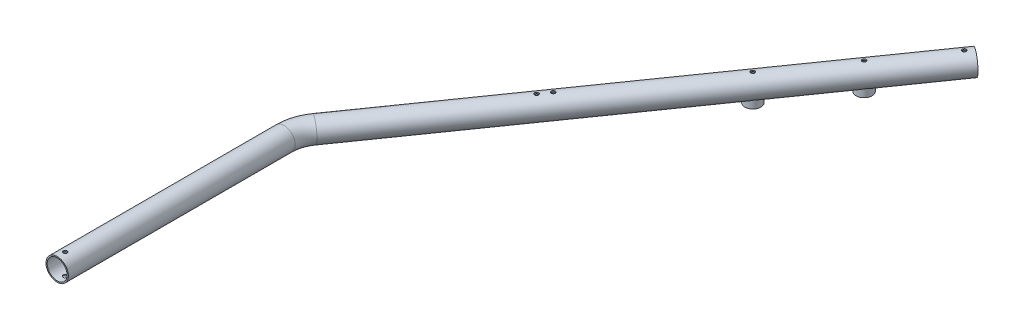
SolidWorks part; units mm, degrees
material "1060 Alloy"
ref_plane "Front Plane" through (0, 0, 0) normal (0, 0, 1) x (1, 0, 0)
ref_plane "Top Plane" through (0, 0, 0) normal (0, 1, 0) x (1, 0, 0)
ref_plane "Right Plane" through (0, 0, 0) normal (1, 0, 0) x (0, 0, -1)
sketch "Sketch2" plane through (0, 0, 0) normal (0, 1, 0) x (1, 0, 0)
  line L0 (0, 0) -> (-340.9616, -487.088)
  line L1 (-350, -515.7611) -> (-350, -800)
  arc A0 (-340.9616, -487.088) -> (-350, -515.7611) centre (-300, -515.7611) ccw
  point P6 (-350, -500)
  dimension "D4" = 50
  dimension "D2" = 500
  dimension "D3" = 300
  dimension "D1" = 350
ref_plane "Plane1" through (0, 0, 800) normal (0, 0, 1) x (1, 0, 0)
sketch "Sketch3" plane through (0, 0, 800) normal (0, 0, 1) x (1, 0, 0)
  circle A0 centre (-350, 0) radius 14
  dimension "D1" = 28
sweep "Sweep1" add profiles "Sketch3" path "Sketch2"
ref_plane "Plane2" through (0, -19.5, 0) normal (0, 1, 0) x (1, 0, 0)
sketch "Sketch7" plane through (0, -19.5, 0) normal (0, 1, 0) x (1, 0, 0)
  line L0 (0, 0) -> (-57.3462, -81.9232) construction
  line L1 (-57.3462, -81.9232) -> (-114.6925, -163.8464) construction
  line L2 (11.4692, -8.0285) -> (-11.4692, 8.0285) construction
  circle A1 centre (-57.3462, -81.9232) radius 10
  circle A2 centre (-114.6925, -163.8464) radius 10
  dimension "D1" = 20
  dimension "D2" = 100
  dimension "D3" = 100
extrude "Boss-Extrude2" add sketch "Sketch7" along normal up to surface (6.7284 mm away) up to face at (-329.4923, 0, 495.1165)
sketch "Sketch4" plane through (0, 0, 0) normal (0, 1, 0) x (1, 0, 0)
  line L0 (0, 0) -> (-340.9616, -487.088) construction
  line L1 (11.4692, -8.0285) -> (-11.4692, 8.0285) construction
  line L2 (-350, -515.7611) -> (-350, -800) construction
  line L3 (-364, -800) -> (-336, -800) construction
  circle A0 centre (-5.7346, -8.1923) radius 2.5
  circle A1 centre (-57.3462, -81.9232) radius 2.5
  circle A2 centre (-114.6925, -163.8464) radius 2.5
  circle A3 centre (-350, -790) radius 2.5
  circle A4 centre (-57.3462, -81.9232) radius 10 construction
  circle A5 centre (-114.6925, -163.8464) radius 10 construction
  dimension "D5" = 5
  dimension "D4" = 5
  dimension "D1" = 10
  dimension "D6" = 10
sketch "Sketch5" plane through (0, 0, 800) normal (0, 0, 1) x (1, 0, 0)
  circle A0 centre (-350, 0) radius 12.5
  circle A1 centre (-350, 0) radius 14 construction
  dimension "D1" = 1.5
sweep "Cut-Sweep1" cut profiles "Sketch5" path "Sketch2<2>"
sketch "Sketch2<2>" plane through (0, 0, 0) normal (0, 1, 0) x (1, 0, 0) same geometry as "Sketch2"
ref_plane "Plane3" through (-258.0581, 0, 368.6544) normal (0.5735, 0, -0.8192) x (-0.8192, 0, -0.5735)
sketch "Sketch8" plane through (-258.0581, 0, 368.6544) normal (0.5735, 0, -0.8192) x (-0.8192, 0, -0.5735)
  circle A0 centre (0, 0) radius 17.5
  dimension "D1" = 35
extrude "Cut-Extrude1" cut sketch "Sketch4" against normal through all both and the other way through all
sketch "Sketch9" plane through (0, 0, 0) normal (0, 1, 0) x (1, 0, 0)
  line L0 (-340.9616, -487.088) -> (0, 0) construction
  line L1 (-329.4923, -495.1165) -> (-352.4308, -479.0595) construction
  circle A0 centre (-217.6672, -310.9531) radius 2.5
  circle A1 centre (-226.2691, -323.2416) radius 2.5
  dimension "D1" = 5
  dimension "D3" = 200
  dimension "D2" = 15
extrude "Cut-Extrude2" cut sketch "Sketch9" against normal through all both and the other way through all
equation "\"keelOutDiameter\"= 1in"
equation "\"poleOutDiameter\"= 28mm"
equation "\"poleLength\"=650mm"
equation "\"propellerTubeOutDiameter\"= 28mm"
equation "\"D1@Sketch3\"=\"poleOutDiameter\""
equation "\"propellerDiameter\"= 700mm"
equation "\"D1@Sketch2\"=\"propellerDiameter\"/2"
